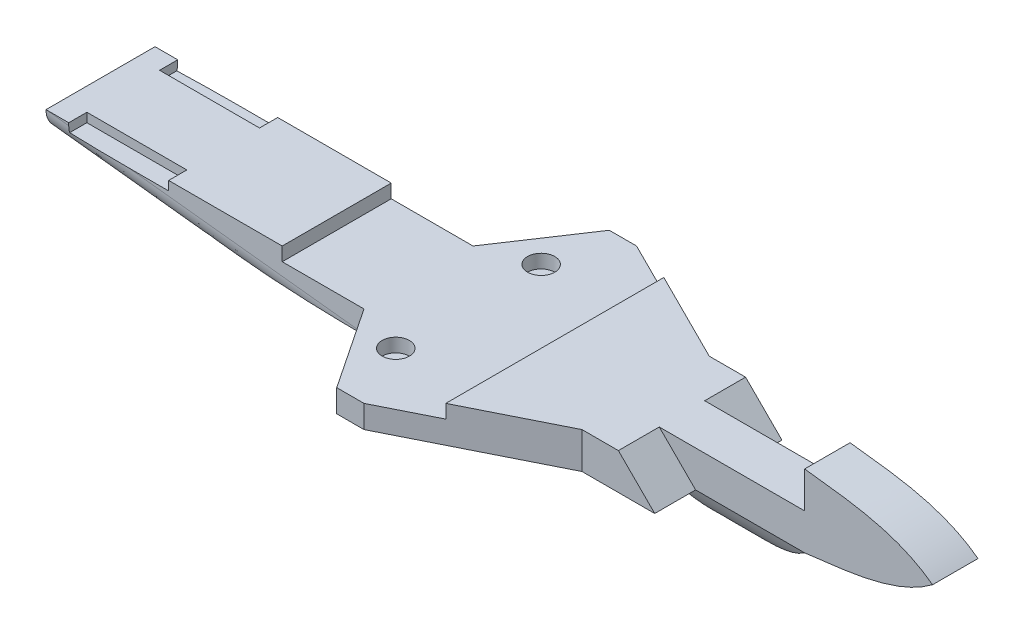
SolidWorks part; units mm, degrees
ref_plane "Front Plane" through (0, 0, 0) normal (0, 0, 1) x (1, 0, 0)
ref_plane "Top Plane" through (0, 0, 0) normal (0, 1, 0) x (1, 0, 0)
ref_plane "Right Plane" through (0, 0, 0) normal (1, 0, 0) x (0, 0, -1)
sketch "Sketch1" plane through (0, 0, 0) normal (0, 1, 0) x (1, 0, 0)
  line L0 (-1, 15) -> (2, 15)
  line L1 (0, 0) -> (1879.8507, 0) construction
  line L2 (2, 15) -> (18, 7)
  line L3 (18, 7) -> (23, 7)
  line L4 (23, 7) -> (23, -7)
  line L5 (-1, 15) -> (-7, 6)
  line L6 (-7, 6) -> (-42, 6)
  line L7 (-42, 6) -> (-42, -6)
  line L8 (-7, -6) -> (-42, -6)
  line L9 (-1, -15) -> (-7, -6)
  line L10 (18, -7) -> (23, -7)
  line L11 (2, -15) -> (18, -7)
  line L12 (-1, -15) -> (2, -15)
  line L13 (-39.5, 6) -> (-39.5, 9)
  line L14 (-39.5, 9) -> (-42, 11.5)
  line L15 (-42, 11.5) -> (-42, 20.5)
  line L16 (-42, 20.5) -> (-39, 20.5)
  line L17 (-39, 20.5) -> (-28.5, 9)
  line L18 (-28.5, 9) -> (-28.5, 6)
  line L19 (-28.5, -9) -> (-28.5, -6)
  line L20 (-39, -20.5) -> (-28.5, -9)
  line L21 (-42, -20.5) -> (-39, -20.5)
  line L22 (-42, -11.5) -> (-42, -20.5)
  line L23 (-39.5, -9) -> (-42, -11.5)
  line L24 (-39.5, -6) -> (-39.5, -9)
  line L25 (2, 15) -> (5.0407, 13.4797)
  line L26 (5.0407, 13.4797) -> (-37.7143, 34.8571)
  line L27 (-18.2143, 6) -> (-37.7143, 27.3571)
  line L28 (-37.7143, 27.3571) -> (-37.7143, 34.8571)
  point P12 (-42, 0)
  point P15 (23, 0)
  point P35 (-37, 36.9014)
  point P36 (-37.8355, 37.4075)
  point P37 (-36.8029, 36.5485)
  point P38 (-37, 28.6458)
  point P39 (-17.4678, 6)
  point P40 (-24.5, 9)
  point P41 (-33.1067, 20.5)
  point P42 (-32.4335, 20.5)
  dimension "D1" = 3
  dimension "D2" = 1
  dimension "D3" = 15
  dimension "D4" = 18
  dimension "D5" = 7
  dimension "D6" = 5
  dimension "D7" = 6
  dimension "D8" = 6
  dimension "D9" = 35
  dimension "D10" = 3
  dimension "D11" = 5.5
  dimension "D12" = 9
  dimension "D13" = 3
  dimension "D14" = 10.5
  dimension "D15" = 3
  dimension "D16" = 11
  dimension "D17" = 2.5
  dimension "D18" = 19.5
  dimension "D19" = 7.5
extrude "Boss-Extrude1" add sketch "Sketch1" along normal blind 4 contours L7 L1 L4 L3 L2 L0 L5 L6 | L1 L7 L8 L9 L12 L11 L10 L4 region at (-5.748, 0, 0)
sketch "Sketch2" plane through (0, 4, 0) normal (0, 1, 0) x (1, 0, 0)
  line L0 (0, 0) -> (-13.3344, 0) construction
  circle A0 centre (-1.5, 8) radius 1.5
  circle A1 centre (-1.5, -8) radius 1.5
  dimension "D1" = 3
  dimension "D2" = 8
  dimension "D3" = 1.5
extrude "Boss-Extrude2" add sketch "Sketch2" along normal blind 3
sketch "Sketch3" plane through (0, 0, 6) normal (0, 0, 1) x (1, 0, 0)
  line L0 (-24, 0) -> (-42, 2)
  line L1 (-7, 0) -> (-42, 0) construction
  line L2 (-42, 4) -> (-42, 0) construction
  line L3 (-42, 2) -> (-42, 0)
  line L4 (-42, 0) -> (-24, 0)
  dimension "D1" = 2
  dimension "D2" = 18
extrude "Cut-Extrude1" cut sketch "Sketch3" against normal blind 13
sketch "Sketch4" plane through (-42, 0, 0) normal (-1, 0, 0) x (0, 0, 1)
  line L0 (-6, 4) -> (6, 4) construction
  line L1 (6, 4) -> (6, 0) construction
  line L2 (-6, 4) -> (-6, 2) construction
  line L3 (-6, 4) -> (-6, 0)
  line L4 (-6, 0) -> (6, 0)
  line L5 (6, 0) -> (6, 4)
  line L6 (-1.25, 2.9103) -> (1.25, 2.9103)
  circle A0 centre (3.5, 4) radius 2.5
  circle A1 centre (-3.5, 4) radius 2.5
  line M1 (-6, 4) -> (-6, 2)
  line M2 (-6, 2) -> (6, 2)
  line M3 (6, 2) -> (6, 4)
  dimension "D1" = 5
  dimension "D2" = 5
  dimension "D3" = 2.5
  dimension "D4" = 2.5
  dimension "D5" = 2.5
extrude "Cut-Extrude2" cut sketch "Sketch4" along direction (-0.9939, 0.1104, 0) on the side against the normal blind 49 contours A1 M1 M2 | A1 A0 L6 M2 | A0 M2 M3 region at (-42, 2.4778, -5.7141) region at (-42, 2.4195, 0) region at (-42, 2.4778, 5.7141)
sketch "Sketch5" plane through (0, 4, 0) normal (0, 1, 0) x (1, 0, 0)
  circle A0 centre (-1.5, 8) radius 1.5
  circle A1 centre (-1.5, -8) radius 1.5
  circle A2 centre (-1.5, -8) radius 1.5 construction
extrude "Cut-Extrude3" cut sketch "Sketch5" against normal blind 3 and the other way blind 49
sketch "Sketch6" plane through (0, 0, 15) normal (0, 0, 1) x (1, 0, 0)
  line L6 (-7, 4) -> (8, 4)
  line L8 (-7, 2.5) -> (8, 2.5)
  line L10 (8, 4) -> (8, 2.5)
  line L11 (-7, 4) -> (-16, 4)
  line L13 (-7, 2.5) -> (-16, 2.5)
  line L14 (-16, 4) -> (-16, 2.5)
  dimension "D1" = 1.5
extrude "Cut-Extrude4" cut sketch "Sketch6" against normal blind 41
sketch "Sketch7" plane through (0, 0, 6) normal (0, 0, 1) x (1, 0, 0)
  line L0 (-16, 4) -> (-42, 4) construction
  line L1 (-39.5, 4) -> (-28.5, 4)
  line L2 (-39.5, 4) -> (-39.5, 3)
  line L3 (-39.5, 3) -> (-28.5, 3)
  line L4 (-28.5, 4) -> (-28.5, 3)
  line L5 (-42, 4) -> (-42, 2) construction
  dimension "D1" = 2.5
  dimension "D2" = 11
  dimension "D3" = 1
extrude "Cut-Extrude5" cut sketch "Sketch7" against normal blind 2
extrude "Cut-Extrude6" cut sketch "Sketch7<2>" along normal blind 2 from surface starting at face at (-17.6, 2.6222, -6)
sketch "Sketch7<2>" plane through (0, 0, 6) normal (0, 0, 1) x (1, 0, 0) same geometry as "Sketch7"
sketch "Sketch8" plane through (-0.2927, -2.6341, 0) normal (-0.1104, -0.9939, 0) x (0.9939, -0.1104, 0)
  line L0 (-41.964, 2) -> (-41.964, 5) construction
  line L1 (-39.464, -2.5) -> (-28.464, -2.5)
  line L2 (-39.464, -2.5) -> (-39.464, -4.5)
  line L3 (-39.464, -4.5) -> (-28.464, -4.5)
  line L4 (-28.464, -2.5) -> (-28.464, -4.5)
  line L5 (-39.464, 4.5) -> (-28.464, 4.5)
  line L6 (-39.464, 4.5) -> (-39.464, 2.5)
  line L7 (-39.464, 2.5) -> (-28.464, 2.5)
  line L8 (-28.464, 4.5) -> (-28.464, 2.5)
  line L9 (-41.964, -5) -> (-41.964, -2) construction
  line L10 (-41.964, 5) -> (-23.8532, 5) construction
  line L11 (-41.964, -2) -> (-23.8532, -2) construction
  dimension "D1" = 2.5
  dimension "D2" = 11
  dimension "D3" = 11
  dimension "D4" = 2.5
  dimension "D5" = 2
  dimension "D6" = 2
  dimension "D7" = 0.5
  dimension "D8" = 0.5
extrude "Cut-Extrude7" cut sketch "Sketch8" against normal blind 1
sketch "Sketch9" plane through (23, 0, 0) normal (1, 0, 0) x (0, 0, -1)
  line L0 (2.5, 0) -> (-2.5, 0)
  line L1 (7, 0) -> (-7, 0) construction
  line L3 (7, 0) -> (-7, 0)
  line L4 (7, 0) -> (7, 4)
  line L5 (7, 4) -> (-7, 4)
  line L6 (-7, 0) -> (-7, 4)
  spline S0 degree 2 poles (2.5, 0) (0.1723, -6.0034) (-2.5, 0) knots 0 0 0 1 1 1
  point P6 (0, 0)
  line M2 (-7, 0) -> (7, 0)
  line M3 (7, 0) -> (7, 4)
  line M4 (7, 4) -> (-7, 4)
  line M5 (-7, 4) -> (-7, 0)
  dimension "D1" = 5
  dimension "D2" = 3
extrude "Boss-Extrude3" add sketch "Sketch9" along normal blind 15 contours M5 M2 M3 M4 | S0 M2 region at (23, -1.2007, -0.0345) region at (23, 2, 0)
sketch "Sketch10" plane through (0, 0, -7) normal (0, 0, -1) x (-1, 0, 0)
  line L0 (-23, 0) -> (-38, 0)
  line L1 (-23, 0) -> (-23, -3.0017)
  line L2 (-23, -3.0017) -> (-23, 0) construction
  line L3 (-38, -3.0017) -> (-23, -3.0017) construction
  line L4 (-23, -3.0017) -> (-38, -3.0017)
  line L5 (-38, -3.0017) -> (-38, 0)
  line L6 (-38, 4) -> (-52.081, 4)
  line L7 (-38, 0) -> (-38, 8)
  spline S0 degree 3 poles (-23, 0) (-25.3156, -3.0796) (-31.0974, -3.102) (-36.3128, -1.3823) (-38, 0) knots 0 0 0 0 0.604337 1 1 1 1
  spline S1 degree 3 poles (-38, 0) (-42.8126, 0.5816) (-48.0984, 1.0129) (-52.081, 4) knots 0 0 0 0 1 1 1 1
  spline S2 degree 3 poles (-38, 8) (-42.8126, 7.4184) (-48.0984, 6.9871) (-52.081, 4) knots 0 0 0 0 1 1 1 1
  line M4 (-38, 4) -> (-38, 0)
extrude "Cut-Extrude8" cut sketch "Sketch10" against normal blind 15 contours L1 S0 L5 L4 region at (23.153, -1.5009, -7)
sketch "Sketch12" plane through (0, 0, 0) normal (0, -1, 0) x (1, 0, 0)
  line L0 (26, 7) -> (26, -7)
  line L1 (18, 7) -> (38, 7) construction
  line L2 (18, -7) -> (38, -7) construction
  line L3 (26, -7) -> (38, -7)
  line L4 (38, -7) -> (38, -2.5)
  line L5 (38, -2.5) -> (23, -2.5)
  line L6 (23, -2.5) -> (23, 2.5)
  line L7 (23, 2.5) -> (38, 2.5)
  line L8 (38, 2.5) -> (38, 7)
  line L9 (38, 7) -> (26, 7)
  line M3 (38, -2.5) -> (23, -2.5)
  line M5 (23, 2.5) -> (38, 2.5)
  line M6 (38, 2.5) -> (38, 7)
  line M7 (38, 7) -> (18, 7)
  line M23 (18, -7) -> (38, -7)
  line M24 (38, -7) -> (38, -2.5)
  dimension "D1" = 12
extrude "Cut-Extrude9" cut sketch "Sketch12" against normal blind 15 contours L0 M3 M23 M24 | L0 M7 M5 M6 region at (32, 0, 4.75) region at (32, 0, -4.75)
extrude "Boss-Extrude4" add sketch "Sketch10<4>" against normal blind 5 from offset 4.5 contours S1 L6 M4 | L7 S2 L6 region at (43.4523, 2.4486, -7) region at (43.4523, 5.5514, -7) offset against normal yes
sketch "Sketch10<4>" plane through (0, 0, -7) normal (0, 0, -1) x (-1, 0, 0) same geometry as "Sketch10"
sketch "Sketch13" plane through (0, 0, 7) normal (0, 0, 1) x (1, 0, 0)
  line L0 (22, 4) -> (26, 0)
  line L1 (18, 4) -> (26, 4) construction
  line L2 (26, 0) -> (26, 4)
  line L3 (26, 4) -> (22, 4)
extrude "Cut-Extrude10" cut sketch "Sketch13" against normal blind 4.5
extrude "Cut-Extrude11" cut sketch "Sketch13<2>" along normal blind 4.5 from surface starting at face at (22, 2, -7)
sketch "Sketch13<2>" plane through (0, 0, 7) normal (0, 0, 1) x (1, 0, 0) same geometry as "Sketch13"
